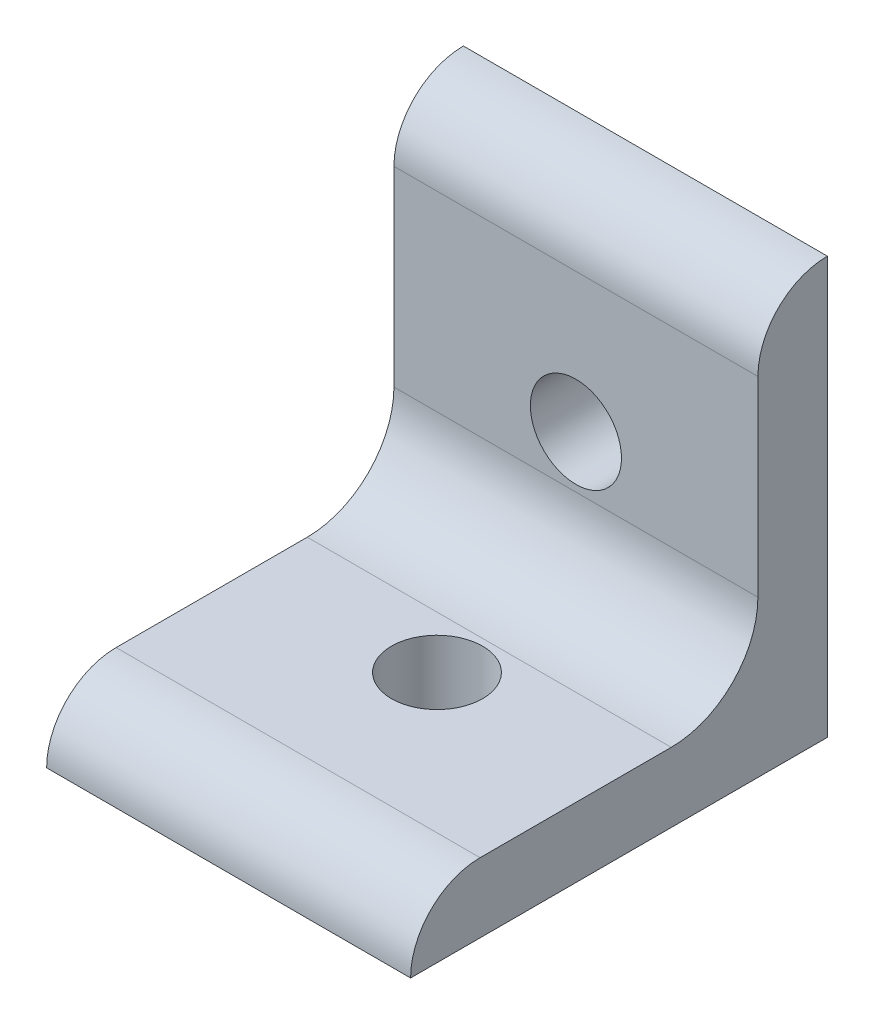
SolidWorks part; units mm, degrees
ref_plane "Front Plane" through (0, 0, 0) normal (0, 0, 1) x (1, 0, 0)
ref_plane "Top Plane" through (0, 0, 0) normal (0, 1, 0) x (1, 0, 0)
ref_plane "Right Plane" through (0, 0, 0) normal (1, 0, 0) x (0, 0, -1)
ref_plane "Plane1" through (16.637, 0, 0) normal (1, 0, 0) x (0, 0, -1)
sketch "Sketch1" plane through (16.637, 0, 0) normal (1, 0, 0) x (0, 0, -1)
  line L0 (-38.1, 0) -> (0, 0)
  line L1 (0, 0) -> (0, 38.1)
  line L2 (-6.35, 31.75) -> (-6.35, 6.35)
  line L3 (-6.35, 6.35) -> (-31.75, 6.35)
  arc A0 (-31.75, 6.35) -> (-38.1, 0) centre (-31.75, 0) ccw
  arc A1 (0, 38.1) -> (-6.35, 31.75) centre (0, 31.75) ccw
extrude "Boss-Extrude1" add sketch "Sketch1" against normal blind 33.274
hole_wizard "Hole1" positions "Sketch3" profile "Sketch2" legacy
sketch "Sketch3" plane through (0, 0, 6.35) normal (0, 0, 1) x (1, 0, 0)
  point P0 (0, 19.05)
sketch "Sketch2" plane through (0, 19.05, 6.35) normal (1, 0, 0) x (0, -1, 0)
  line L0 (0, 0) -> (0, 6.35)
  line L1 (0, 6.35) -> (4.1656, 6.35)
  line L2 (4.1656, 6.35) -> (4.1656, 0)
  line L3 (4.1656, 0) -> (0, 0)
  line L4 (0, 110) -> (0, -10) construction
  dimension "Diameter" = 8.3312
  dimension "Depth" = 6.35
hole_wizard "Hole2" positions "Sketch5" profile "Sketch4" legacy
sketch "Sketch5" plane through (0, 6.35, 0) normal (0, 1, 0) x (1, 0, 0)
  point P0 (0, -19.05)
sketch "Sketch4" plane through (0, 6.35, 19.05) normal (1, 0, 0) x (0, 0, 1)
  line L0 (0, 0) -> (0, 6.35)
  line L1 (0, 6.35) -> (4.1656, 6.35)
  line L2 (4.1656, 6.35) -> (4.1656, 0)
  line L3 (4.1656, 0) -> (0, 0)
  line L4 (0, 110) -> (0, -10) construction
  dimension "Diameter" = 8.3312
  dimension "Depth" = 6.35
fillet "Fillet1" radius 7.9248 1 edges at (0, 6.35, 6.35) tangent propagation no
